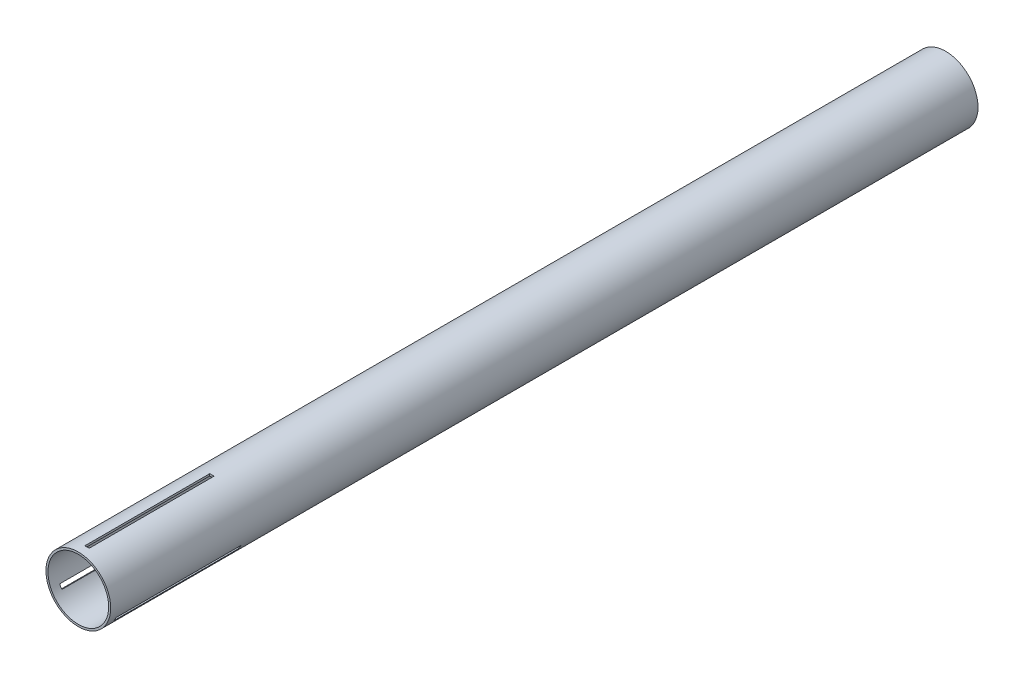
SolidWorks part; units mm, degrees
ref_plane "Front Plane" through (0, 0, 0) normal (0, 0, 1) x (1, 0, 0)
ref_plane "Top Plane" through (0, 0, 0) normal (0, 1, 0) x (1, 0, 0)
ref_plane "Right Plane" through (0, 0, 0) normal (1, 0, 0) x (0, 0, -1)
sketch "Sketch1" plane through (0, 0, 0) normal (0, 0, 1) x (1, 0, 0)
  circle A0 centre (0, 0) radius 23.6982
  circle A1 centre (0, 0) radius 22.225
extrude "Boss-Extrude1" add sketch "Sketch1" along normal blind 635
ref_plane "Plane1" through (0, 50.8, 0) normal (0, 1, 0) x (1, 0, 0)
sketch "Sketch3" plane through (0, 50.8, 0) normal (0, 1, 0) x (1, 0, 0)
  line L0 (-23.6982, -635) -> (23.6982, -635) construction
  line L2 (1.5875, -628.65) -> (1.5875, -537.21)
  line L3 (-1.5875, -628.65) -> (-1.5875, -537.21)
  line L4 (-1.5875, -537.21) -> (1.5875, -537.21)
  line L5 (-1.5875, -628.65) -> (1.5875, -628.65)
  dimension "D1" = 6.35
extrude "Cut-Extrude2" cut sketch "Sketch3" against normal up to next and the other way through all
pattern_circular "CirPattern4" count 3 over 360 about axis through (0, 0, 635) along (0, 0, 1) of "Cut-Extrude2"
